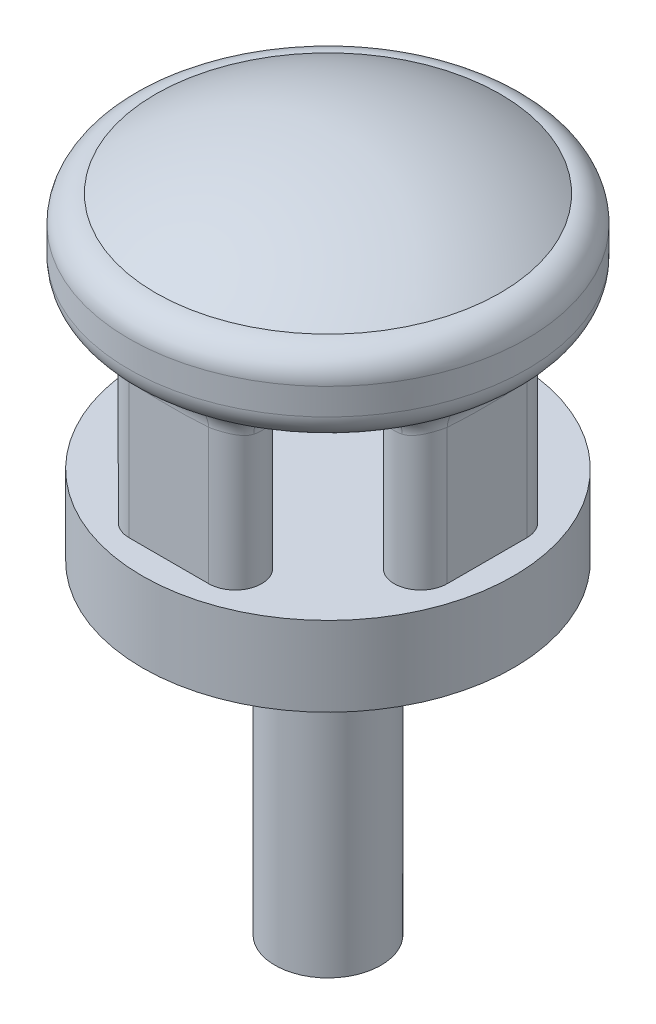
SolidWorks part; units mm, degrees
ref_plane "Front Plane" through (0, 0, 0) normal (0, 0, 1) x (1, 0, 0)
ref_plane "Top Plane" through (0, 0, 0) normal (0, 1, 0) x (1, 0, 0)
ref_plane "Right Plane" through (0, 0, 0) normal (1, 0, 0) x (0, 0, -1)
sketch "Sketch1" plane through (0, 0, 0) normal (0, 1, 0) x (1, 0, 0)
  circle A0 centre (0, 0) radius 9.525
  dimension "D1" = 19.05
extrude "button top" add sketch "Sketch1" along normal blind 3.81
sketch "Sketch2" plane through (0, 0, 0) normal (0, -1, 0) x (1, 0, 0)
  line L9 (-1.905, 6.35) -> (1.905, 6.35) construction
  line L10 (-1.905, 7.62) -> (1.905, 7.62)
  line L11 (-1.905, 5.08) -> (1.905, 5.08)
  arc A6 (-1.905, 7.62) -> (-1.905, 5.08) centre (-1.905, 6.35) ccw
  arc A7 (1.905, 5.08) -> (1.905, 7.62) centre (1.905, 6.35) ccw
  point P22 (0, 6.35)
  dimension "D2" = 1.27
  dimension "D1" = 6.35
  dimension "D8" = 3.81
extrude "connecting leg" add sketch "Sketch2" along normal blind 7.62
ref_axis "central axis" through (0, 3.81, 0) along (0, -1, 0)
pattern_circular "moar legs" count 4 over 360 about axis through (0, 3.81, 0) along (0, -1, 0) of "connecting leg"
ref_plane "base plane" through (0, -7.62, 0) normal (0, -1, 0) x (-1, 0, 0)
sketch "Sketch3" plane through (0, -7.62, 0) normal (0, -1, 0) x (-1, 0, 0)
  circle A0 centre (0, 0) radius 8.89
extrude "base" add sketch "Sketch3" along normal blind 3.81
fillet "round top" radius 1.27 2 edges at (0, 3.81, 9.525) (0, 0, 9.525)
fillet "round bars" radius 1.27 16 edges at (0, 0, 5.08) (-3.175, 0, 6.35) (0, 0, 7.62) (3.175, 0, 6.35) (5.08, 0, 0) (6.35, 0, 3.175) (7.62, 0, 0) (6.35, 0, -3.175) (3.175, 0, -6.35) (0, 0, -7.62) (-3.175, 0, -6.35) (0, 0, -5.08) (-5.08, 0, 0) (-6.35, 0, -3.175) (-7.62, 0, 0) (-6.35, 0, 3.175)
dome "button ness" faces to dome 1 distance 2.54 reverse direction no elliptical dome no face at (0, 3.81, 8.255) parameters "D1"=2.54
ref_point "center of face"
sketch "Sketch6" plane through (0, -11.43, 0) normal (0, -1, 0) x (1, 0, 0)
  circle A0 centre (0, 0) radius 2.54
extrude "flag" add sketch "Sketch6" along normal blind 15.5169
fillet "flag fillet" radius 2.54 1 edges at (0, -11.43, -2.54)
